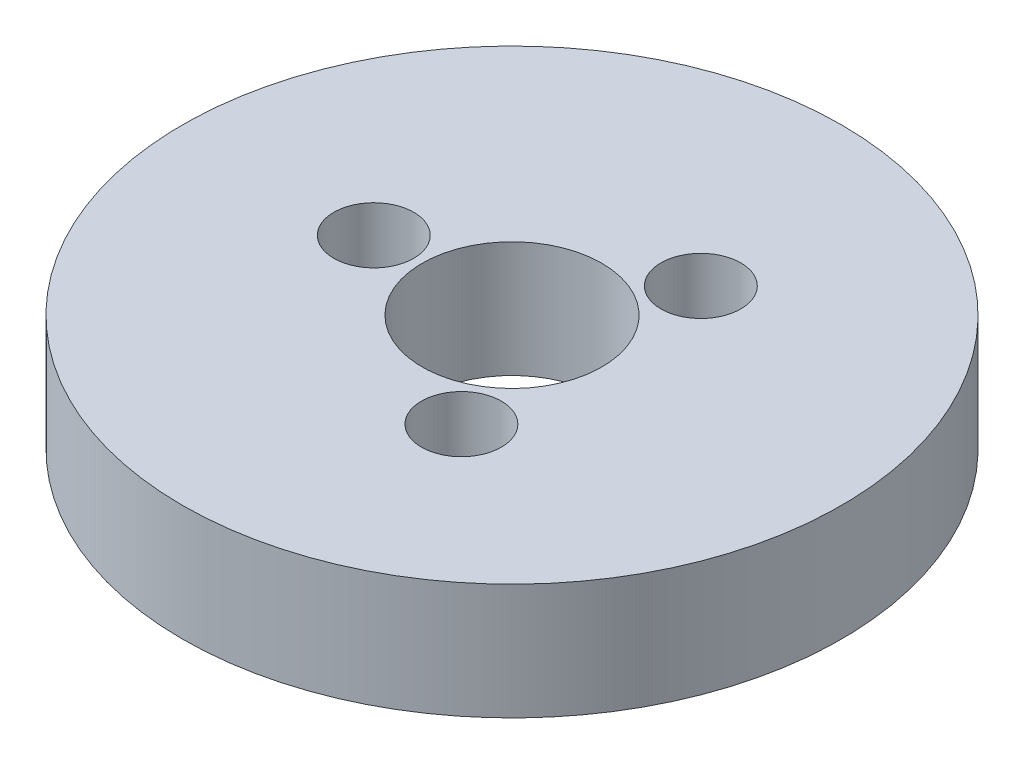
SolidWorks part; units mm, degrees
ref_plane "Front Plane" through (0, 0, 0) normal (0, 0, 1) x (1, 0, 0)
ref_plane "Top Plane" through (0, 0, 0) normal (0, 1, 0) x (1, 0, 0)
ref_plane "Right Plane" through (0, 0, 0) normal (1, 0, 0) x (0, 0, -1)
sketch "Sketch1" plane through (0, 0, 0) normal (0, 1, 0) x (1, 0, 0)
  circle A0 centre (0, 0) radius 82.5
  dimension "FLANGE_OD" = 165
extrude "Boss-Extrude1" add sketch "Sketch1" along normal blind 29
sketch "Sketch2" plane through (0, 0, 0) normal (0, 1, 0) x (1, 0, 0)
  circle A0 centre (0, 0) radius 22.5
  dimension "BORE_D" = 45
extrude "Cut-Extrude1" cut sketch "Sketch2" along normal through all
sketch "Sketch3" plane through (0, 29, 0) normal (0, 1, 0) x (1, 0, 0)
  circle A0 centre (0, 0) radius 34.605 construction
  circle A1 centre (-34.605, 0) radius 10
  dimension "BOLT_D" = 20
  dimension "BOLT_PCD" = 69.2101
extrude "Cut-Extrude2" cut sketch "Sketch3" against normal blind 19.8976
pattern_circular "CirPattern1" count 3 over 360 about axis through (0, 0, 0) along (0, 1, 0) of "Cut-Extrude2"
